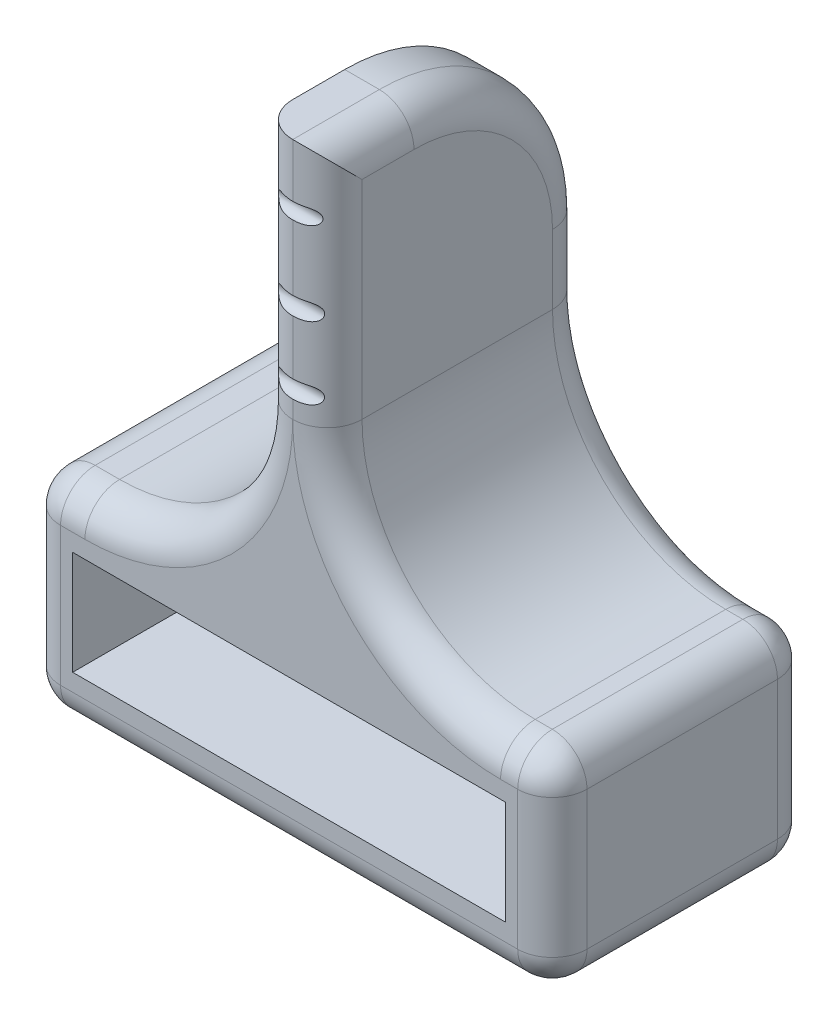
SolidWorks part; units mm, degrees
ref_plane "Front Plane" through (0, 0, 0) normal (0, 0, 1) x (1, 0, 0)
ref_plane "Top Plane" through (0, 0, 0) normal (0, 1, 0) x (1, 0, 0)
ref_plane "Right Plane" through (0, 0, 0) normal (1, 0, 0) x (0, 0, -1)
sketch "Sketch1" plane through (0, 0, 0) normal (0, 1, 0) x (1, 0, 0)
  line L1 (-41.6963, 19.6283) -> (-11.2963, 19.6283)
  line L2 (-41.6963, 19.6283) -> (-41.6963, 4.6283)
  line L3 (-41.6963, 4.6283) -> (-11.2963, 4.6283)
  line L4 (-11.2963, 19.6283) -> (-11.2963, 4.6283)
  dimension "D1" = 30.4
  dimension "D2" = 15
extrude "Boss-Extrude1" add sketch "Sketch1" along normal blind 12
sketch "Sketch2" plane through (0, 0, -4.6283) normal (0, 0, 1) x (1, 0, 0)
  line L0 (-41.6963, 12) -> (-11.2963, 12) construction
  line L1 (-38.9963, 9) -> (-13.9963, 9)
  line L2 (-38.9963, 9) -> (-38.9963, 3)
  line L3 (-38.9963, 3) -> (-13.9963, 3)
  line L4 (-13.9963, 9) -> (-13.9963, 3)
  line L5 (-11.2963, 12) -> (-11.2963, 0) construction
  dimension "D1" = 25
  dimension "D2" = 6
  dimension "D3" = 3
  dimension "D4" = 2.7
extrude "Cut-Extrude1" cut sketch "Sketch2" against normal through all
sketch "Sketch3" plane through (0, 12, 0) normal (0, 1, 0) x (1, 0, 0)
  line L0 (-26.0928, 19.0641) -> (-26.4963, 4.6283) construction
  line L1 (-41.6963, 4.6283) -> (-11.2963, 4.6283) construction
  line L2 (-11.2963, 19.6283) -> (-41.6963, 19.6283) construction
  line L3 (-24.2867, 4.6283) -> (-28.2867, 4.6283)
  line L4 (-24.2867, 4.6283) -> (-24.2867, 19.6283)
  line L5 (-24.2867, 19.6283) -> (-28.2867, 19.6283)
  line L6 (-28.2867, 4.6283) -> (-28.2867, 19.6283)
  line L7 (-24.2867, 4.6283) -> (-28.2867, 19.6283) construction
  line L8 (-24.2867, 19.6283) -> (-28.2867, 4.6283) construction
  point P4 (-26.2867, 12.1283)
  dimension "D1" = 15
  dimension "D2" = 4
extrude "Boss-Extrude2" add sketch "Sketch3" along normal blind 24
sketch "Sketch4" plane through (-24.2867, 0, 0) normal (1, 0, 0) x (0, 0, -1)
  line L0 (4.6283, 36) -> (4.6283, 12) construction
  circle A0 centre (4.6283, 14.844) radius 1
fillet "Fillet1" radius 10 2 edges
fillet "Fillet2" radius 10 1 edges at (-26.2867, 36, -19.6283)
sketch "Sketch5" plane through (-11.2963, 0, 0) normal (1, 0, 0) x (0, 0, -1)
  line L1 (7.3812, 7.4827) -> (15.3812, 7.4827)
  line L2 (7.3812, 7.4827) -> (7.3812, 4.4827)
  line L3 (7.3812, 4.4827) -> (15.3812, 4.4827)
  line L4 (15.3812, 7.4827) -> (15.3812, 4.4827)
  dimension "D1" = 8
  dimension "D2" = 3
sketch "Sketch6" plane through (-24.2867, 0, 0) normal (1, 0, 0) x (0, 0, -1)
  line L0 (4.6283, 36) -> (4.6283, 22) construction
  circle A0 centre (4.6283, 32.4417) radius 0.464
  circle A1 centre (4.6283, 27.6911) radius 0.5119
  circle A2 centre (4.6283, 23.5231) radius 0.5061
extrude "Cut-Extrude2" cut sketch "Sketch6" against normal through all
fillet "Fillet3" radius 2 21 edges at (-31.2156, 14.9289, -4.6283) (-21.3577, 14.9289, -4.6283) (-24.2867, 36, -7.1283) (-24.2867, 33.0711, -16.6994) (-21.3577, 14.9289, -19.6283) (-41.6963, 6, -19.6283) (-11.2963, 6, -19.6283) (-26.4963, 0, -19.6283) (-41.6963, 0, -12.1283) (-41.6963, 12, -12.1283) (-11.2963, 12, -12.1283) (-11.2963, 0, -12.1283) (-41.6963, 6, -4.6283) (-26.4963, 0, -4.6283) (-11.2963, 6, -4.6283)
